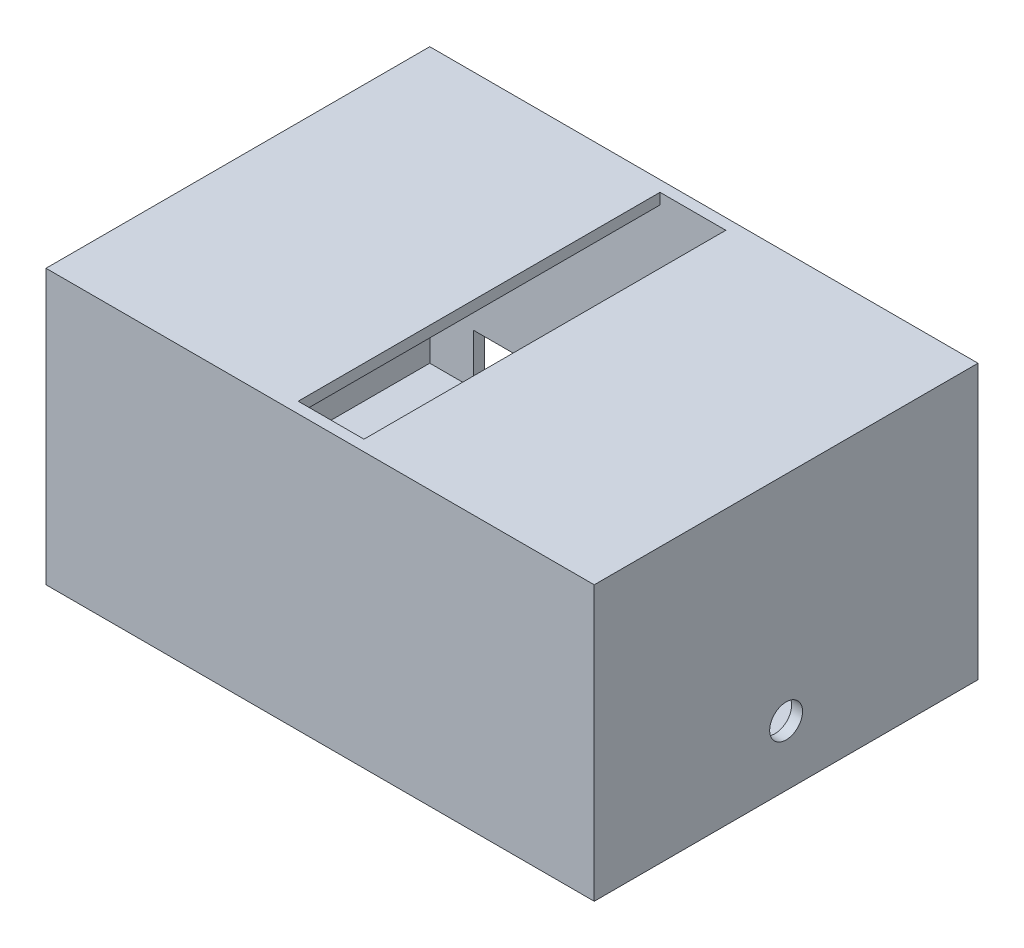
SolidWorks part; units mm, degrees
ref_plane "Front Plane" through (0, 0, 0) normal (0, 0, 1) x (1, 0, 0)
ref_plane "Top Plane" through (0, 0, 0) normal (0, 1, 0) x (1, 0, 0)
ref_plane "Right Plane" through (0, 0, 0) normal (1, 0, 0) x (0, 0, -1)
sketch "Sketch1" plane through (0, 0, 0) normal (0, 1, 0) x (1, 0, 0)
  line L0 (250, 0) -> (0, 0) construction
  line L1 (0, 0) -> (-250, 0) construction
  line L2 (-125, -87.5) -> (125, -87.5)
  line L3 (-125, -87.5) -> (-125, 87.5)
  line L4 (125, -87.5) -> (125, 87.5)
  line L5 (-125, 87.5) -> (125, 87.5)
  line L6 (-125, -87.5) -> (125, 87.5) construction
  line L7 (125, -87.5) -> (-125, 87.5) construction
  dimension "D1" = 175
  dimension "D2" = 250
extrude "Boss-Extrude1" add sketch "Sketch1" against normal blind 125
sketch "Sketch2" plane through (0, -125, 0) normal (0, -1, 0) x (1, 0, 0)
  line L0 (-125, 87.5) -> (125, 87.5) construction
  line L1 (-120, -82.5) -> (120, -82.5)
  line L2 (-120, -82.5) -> (-120, 82.5)
  line L3 (-120, 82.5) -> (120, 82.5)
  line L4 (120, -82.5) -> (120, 82.5)
  line L5 (-120, -82.5) -> (120, 82.5) construction
  line L6 (-120, 82.5) -> (120, -82.5) construction
  line L7 (125, 87.5) -> (125, -87.5) construction
  point P0 (0, 0)
  dimension "D1" = 5
  dimension "D2" = 5
extrude "Cut-Extrude1" cut sketch "Sketch2" against normal offset from surface (120 mm away) 5 up to face at (0, 0, 0)
sketch "Sketch3" plane through (0, 0, 0) normal (0, 1, 0) x (1, 0, 0)
  line L0 (-125, 0) -> (125, 0) construction
  line L1 (-125, 87.5) -> (-125, -87.5) construction
  line L2 (125, -87.5) -> (125, 87.5) construction
  line L3 (0, 87.5) -> (0, -120.2082) construction
  line L4 (-15, -82.5) -> (15, -82.5)
  line L5 (-15, -82.5) -> (-15, 82.5)
  line L6 (-15, 82.5) -> (15, 82.5)
  line L7 (15, -82.5) -> (15, 82.5)
  line L8 (-15, -82.5) -> (15, 82.5) construction
  line L9 (-15, 82.5) -> (15, -82.5) construction
  line L10 (125, 87.5) -> (-125, 87.5) construction
  point P6 (0, 0)
  dimension "D1" = 30
  dimension "D2" = 5
extrude "Cut-Extrude2" cut sketch "Sketch3" against normal through all
sketch "Sketch4" plane through (-125, 0, 0) normal (-1, 0, 0) x (0, 0, 1)
  line L0 (0, 0) -> (0, -125) construction
  line L1 (-87.5, -125) -> (87.5, -125) construction
  circle A0 centre (0, -97.5) radius 7.5
  point P7 (0, -62.5)
  point P8 (0, -62.5)
  point P10 (0, -97.5)
  dimension "D1" = 35
  dimension "D2" = 15
extrude "Cut-Extrude3" cut sketch "Sketch4" against normal through all
sketch "Sketch6" plane through (0, -125, 0) normal (0, -1, 0) x (1, 0, 0)
  line L1 (-125, 87.5) -> (125, 87.5)
  line L2 (-125, 87.5) -> (-125, -87.5)
  line L3 (-125, -87.5) -> (125, -87.5)
  line L4 (125, 87.5) -> (125, -87.5)
extrude "Boss-Extrude2" add sketch "Sketch6" against normal blind 5
sketch "Sketch7" plane through (0, 0, -87.5) normal (0, 0, -1) x (-1, 0, 0)
  line L0 (0, 0) -> (0, -125) construction
  line L1 (-125, -125) -> (125, -125) construction
  line L3 (-100, -120) -> (100, -120)
  line L4 (-100, -120) -> (-100, -97)
  line L5 (-100, -97) -> (100, -97)
  line L6 (100, -120) -> (100, -97)
  line L7 (-100, -120) -> (100, -97) construction
  line L8 (-100, -97) -> (100, -120) construction
  point P5 (0, -108.5)
  dimension "D1" = 200
  dimension "D2" = 23
  dimension "D3" = 5
extrude "Cut-Extrude4" cut sketch "Sketch7" against normal up to surface (5 mm away) up to face at (0, -32.5, -82.5)
